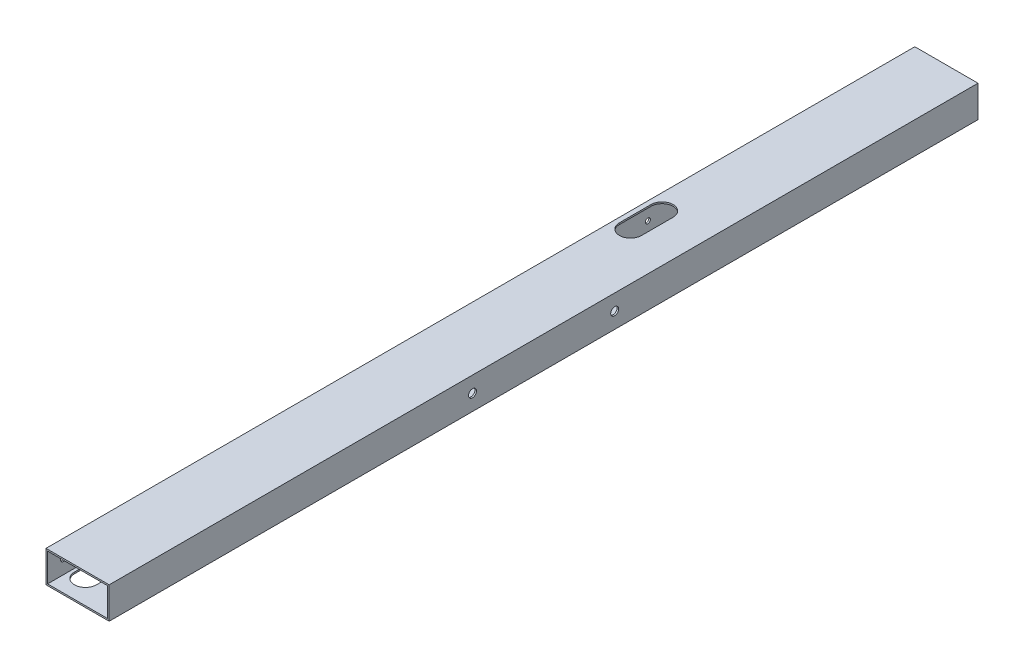
SolidWorks part; units mm, degrees
material "1060 合金"
ref_plane "前视基准面" through (0, 0, 0) normal (0, 0, 1) x (1, 0, 0)
ref_plane "上视基准面" through (0, 0, 0) normal (0, 1, 0) x (1, 0, 0)
ref_plane "右视基准面" through (0, 0, 0) normal (1, 0, 0) x (0, 0, -1)
other "Configuration Table"
sketch "草图1" plane through (0, 0, 0) normal (0, 0, 1) x (1, 0, 0)
  line L1 (0, 0) -> (40, 0)
  line L2 (0, 0) -> (0, -20)
  line L3 (0, -20) -> (40, -20)
  line L4 (40, 0) -> (40, -20)
  dimension "D1" = 20
  dimension "D2" = 40
extrude "拉伸-薄壁1" add sketch "草图1" along normal blind 550 thin thin type one direction reverse wall 1
sketch "草图4" plane through (0, 0, 0) normal (-1, 0, 0) x (0, 0, 1)
  line L0 (550, 0) -> (0, 0) construction
  line L1 (550, 0) -> (550, -20) construction
  line L4 (0, -180.2783) -> (0, 689.7217) construction
  circle A1 centre (539.9964, -10) radius 1.75
  circle A49 centre (10, -10) radius 1.75
  dimension "D27" = 3.5
  dimension "D28" = 3.5
  dimension "D29" = 10
  dimension "D25" = 10
  dimension "D26" = 10.0036
  dimension "D30" = 10
extrude "切除-拉伸2" cut sketch "草图4" against normal blind 1.5
sketch "草图5" plane through (0, 0, 0) normal (-1, 0, 0) x (0, 0, 1)
  circle A0 centre (42.5, -10) radius 1.75 construction
  circle A1 centre (42.5, -10) radius 1.75
  circle A2 centre (62.5, -10) radius 1.75
  circle A3 centre (82.5, -10) radius 1.75
  circle A4 centre (102.5, -10) radius 1.75
  circle A5 centre (122.5, -10) radius 1.75
  circle A6 centre (142.5, -10) radius 1.75
  circle A7 centre (162.5, -10) radius 1.75
  circle A8 centre (182.5, -10) radius 1.75
  circle A9 centre (202.5, -10) radius 1.75
  circle A10 centre (222.5, -10) radius 1.75
  circle A11 centre (242.5, -10) radius 1.75
  circle A12 centre (262.5, -10) radius 1.75
  circle A13 centre (282.5, -10) radius 1.75
  circle A14 centre (302.5, -10) radius 1.75
  circle A15 centre (322.5, -10) radius 1.75
  circle A16 centre (342.5, -10) radius 1.75
  circle A17 centre (362.5, -10) radius 1.75
  circle A18 centre (382.5, -10) radius 1.75
  circle A19 centre (402.5, -10) radius 1.75
  circle A20 centre (422.5, -10) radius 1.75
  circle A21 centre (442.5, -10) radius 1.75
  circle A22 centre (462.5, -10) radius 1.75
  circle A23 centre (482.5, -10) radius 1.75
  dimension "D1" = 23
sketch "草图6" plane through (40, 0, 0) normal (1, 0, 0) x (0, 0, -1)
  line L0 (-550, -20) -> (0, -20) construction
  line L1 (-550, -20) -> (-550, 0) construction
  circle A0 centre (-320, -10) radius 2.5
  circle A1 centre (-230, -10) radius 2.5
  dimension "D1" = 5
  dimension "D2" = 5
  dimension "D3" = 10
  dimension "D4" = 10
  dimension "D5" = 230
  dimension "D6" = 230
extrude "切除-拉伸3" cut sketch "草图6" against normal through all
sketch "草图7" plane through (0, 0, 0) normal (-1, 0, 0) x (0, 0, 1)
  line L0 (550, -20) -> (0, -20) construction
  line L1 (0, 0) -> (0, -20) construction
  circle A0 centre (190, -10) radius 1.6
  circle A1 centre (170, -10) radius 1.6
  dimension "D1" = 3.2
  dimension "D2" = 3.2
  dimension "D3" = 10
  dimension "D4" = 10
  dimension "D5" = 170
  dimension "D6" = 20
extrude "切除-拉伸4" cut sketch "草图7" against normal blind 10
sketch "草图8" plane through (0, -20, 0) normal (0, -1, 0) x (1, 0, 0)
  line L0 (10, 15) -> (10, 25) construction
  line L1 (3, 15) -> (3, 25)
  line L2 (17, 15) -> (17, 25)
  line L3 (0, 550) -> (0, 0) construction
  line L4 (0, 0) -> (40, 0) construction
  arc A0 (3, 15) -> (17, 15) centre (10, 15) ccw
  arc A1 (17, 25) -> (3, 25) centre (10, 25) ccw
  point P2 (10, 20)
  dimension "D2" = 7
  dimension "D1" = 10
  dimension "D3" = 15
  dimension "D4" = 10
extrude "切除-拉伸5" cut sketch "草图8" against normal blind 10
pattern_linear "阵列(线性)2" count 2 spacing 510 along (0, 0, 1) of "切除-拉伸5"
sketch "草图9" plane through (0, 0, 0) normal (0, 1, 0) x (1, 0, 0)
  line L0 (10, -190) -> (10, -170) construction
  line L1 (3, -190) -> (3, -170)
  line L2 (17, -190) -> (17, -170)
  line L3 (0, -550) -> (0, 0) construction
  line L4 (40, 0) -> (0, 0) construction
  arc A0 (3, -190) -> (17, -190) centre (10, -190) ccw
  arc A1 (17, -170) -> (3, -170) centre (10, -170) ccw
  point P2 (10, -180)
  dimension "D2" = 7
  dimension "D1" = 10
  dimension "D3" = 170
  dimension "D4" = 20
extrude "切除-拉伸6" cut sketch "草图9" against normal blind 10
